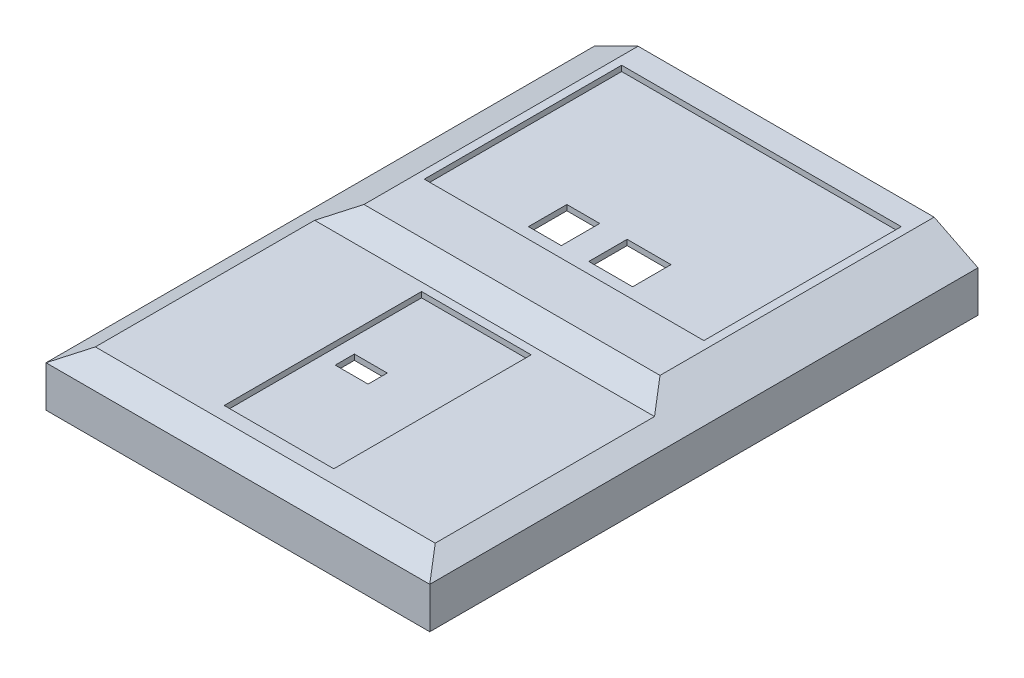
SolidWorks part; units mm, degrees
ref_plane "Ebene vorne" through (0, 0, 0) normal (0, 0, 1) x (1, 0, 0)
ref_plane "Ebene oben" through (0, 0, 0) normal (0, 1, 0) x (1, 0, 0)
ref_plane "Ebene rechts" through (0, 0, 0) normal (1, 0, 0) x (0, 0, -1)
sketch "Skizze1" plane through (0, 0, 0) normal (0, 0, 1) x (1, 0, 0)
  line L1 (-35, -7.5) -> (35, -7.5)
  line L2 (-35, -7.5) -> (-35, 7.5)
  line L3 (-35, 7.5) -> (35, 7.5)
  line L4 (35, -7.5) -> (35, 7.5)
  line L5 (-35, -7.5) -> (35, 7.5) construction
  line L6 (-35, 7.5) -> (35, -7.5) construction
  point P0 (0, 0)
  dimension "D1" = 70
  dimension "D2" = 15
extrude "Aufsatz-Linear austragen1" add sketch "Skizze1" along normal blind 100
sketch "Skizze2" plane through (0, 0, 100) normal (0, 0, 1) x (1, 0, 0)
  line L0 (-35, 7.5) -> (-35, 0)
  line L1 (-35, 7.5) -> (-35, -7.5) construction
  line L2 (-35, 0) -> (-20, 7.5)
  line L3 (35, 7.5) -> (-35, 7.5) construction
  line L4 (-20, 7.5) -> (-35, 7.5)
  dimension "D1" = 15
extrude "Schnitt-Linear austragen1" cut sketch "Skizze2" against normal up to surface (100 mm away) up to face at (0, 0, 0)
ref_plane "Ebene1" through (0, 0, 0) normal (-1, 0, 0) x (0, 0, 1)
mirror "Spiegeln1" about plane through (0, 0, 0) normal (-1, 0, 0) of "Schnitt-Linear austragen1"
sketch "Skizze4" plane through (-35, 0, 0) normal (-1, 0, 0) x (0, 0, 1)
  line L0 (100, 0) -> (95, 2)
  line L1 (95, 2) -> (55, 2)
  line L2 (55, 2) -> (50, 4)
  line L3 (50, 4) -> (0, 4)
  line L5 (0, 7.5) -> (100, 7.5) construction
  line L6 (0, 7.5) -> (100, 7.5)
  line L7 (100, 7.5) -> (100, 0)
  line L8 (0, 0) -> (0, 7.5) construction
  line L9 (0, 4) -> (0, 7.5)
  dimension "D1" = 2
  dimension "D2" = 2
  dimension "D3" = 40
  dimension "D4" = 50
extrude "Schnitt-Linear austragen3" cut sketch "Skizze4" against normal up to surface (70 mm away) up to face at (35, -3.75, 50)
shell "Wandung1" thickness 2 removed face at (0, -7.5, 50)
sketch "Skizze5" plane through (0, 2, 0) normal (0, 1, 0) x (1, 0, 0)
  line L0 (0, 4.125) -> (0, -4.125) construction
  line L1 (-10, -92.5) -> (10, -92.5)
  line L2 (-10, -92.5) -> (-10, -56.5)
  line L3 (-10, -56.5) -> (10, -56.5)
  line L4 (10, -92.5) -> (10, -56.5)
  line L5 (-10, -92.5) -> (10, -56.5) construction
  line L6 (-10, -56.5) -> (10, -92.5) construction
  line L7 (31, -55) -> (-31, -55) construction
  point P0 (0, -74.5)
  dimension "D1" = 36
  dimension "D2" = 20
  dimension "D3" = 1.5
extrude "Schnitt-Linear austragen4" cut sketch "Skizze5" against normal blind 1
sketch "Skizze6" plane through (0, 1, 0) normal (0, 1, 0) x (1, 0, 0)
  line L0 (-10, -56.5) -> (-10, -92.5) construction
  line L1 (-7.25, -71.5) -> (-1.25, -71.5)
  line L2 (-7.25, -71.5) -> (-7.25, -75)
  line L3 (-7.25, -75) -> (-1.25, -75)
  line L4 (-1.25, -71.5) -> (-1.25, -75)
  line L5 (10, -56.5) -> (-10, -56.5) construction
  dimension "D1" = 2.75
  dimension "D2" = 15
  dimension "D3" = 3.5
  dimension "D4" = 6
extrude "Schnitt-Linear austragen5" cut sketch "Skizze6" against normal up to surface (1 mm away) up to face at (0, 0, 74.6148)
sketch "Skizze7" plane through (0, 4, 0) normal (0, 1, 0) x (1, 0, 0)
  line L1 (25.5, -4.5) -> (-25.5, -4.5)
  line L2 (25.5, -4.5) -> (25.5, -40.5)
  line L3 (25.5, -40.5) -> (-25.5, -40.5)
  line L4 (-25.5, -4.5) -> (-25.5, -40.5)
  line L5 (25.5, -4.5) -> (-25.5, -40.5) construction
  line L6 (25.5, -40.5) -> (-25.5, -4.5) construction
  line L7 (27, -50) -> (27, 0) construction
  line L8 (27, 0) -> (-27, 0) construction
  point P0 (0, -22.5)
  dimension "D1" = 51
  dimension "D2" = 36
  dimension "D3" = 1.5
  dimension "D4" = 4.5
extrude "Schnitt-Linear austragen6" cut sketch "Skizze7" against normal blind 1
sketch "Skizze12" plane through (0, 3, 0) normal (0, 1, 0) x (1, 0, 0)
  line L0 (25.5, -40.5) -> (25.5, -4.5) construction
  line L1 (9.5, -37.5) -> (1.5, -37.5)
  line L2 (9.5, -37.5) -> (9.5, -30.5)
  line L3 (9.5, -30.5) -> (1.5, -30.5)
  line L4 (1.5, -37.5) -> (1.5, -30.5)
  line L5 (25.5, -4.5) -> (-25.5, -4.5) construction
  dimension "D1" = 7
  dimension "D2" = 8
  dimension "D3" = 16
  dimension "D4" = 26
extrude "Schnitt-Linear austragen8" cut sketch "Skizze12" against normal up to surface (1 mm away) up to face at (0, 2, 25.8074)
sketch "Skizze13" plane through (0, 0, 0) normal (0, 0, -1) x (-1, 0, 0)
  line L0 (2.5, -7.5) -> (-2.5, -7.5)
  line L1 (35, -7.5) -> (-35, -7.5) construction
  line L2 (-2.5, -7.5) -> (-2.5, -6.2)
  line L3 (-2.5, -6.2) -> (-7.5, -6.2)
  line L4 (-7.5, -6.2) -> (-7.5, -1.9)
  line L5 (-7.5, -1.9) -> (7.5, -1.9)
  line L6 (7.5, -1.9) -> (7.5, -6.2)
  line L7 (7.5, -6.2) -> (2.5, -6.2)
  line L8 (2.5, -6.2) -> (2.5, -7.5)
  line L9 (0, -4.125) -> (0, 4.125) construction
  dimension "D1" = 2.5
  dimension "D2" = 2.5
  dimension "D3" = 5
  dimension "D4" = 5
  dimension "D5" = 1.3
  dimension "D6" = 4.3
extrude "Schnitt-Linear austragen9" cut sketch "Skizze13" against normal blind 1
sketch "Skizze14" plane through (0, 3, 0) normal (0, 1, 0) x (1, 0, 0)
  line L0 (1.5, -30.5) -> (1.5, -37.5) construction
  line L1 (-3.5, -37.5) -> (-9.5, -37.5)
  line L2 (-3.5, -37.5) -> (-3.5, -30.5)
  line L3 (-3.5, -30.5) -> (-9.5, -30.5)
  line L4 (-9.5, -37.5) -> (-9.5, -30.5)
  line L5 (-25.5, -40.5) -> (25.5, -40.5) construction
  dimension "D1" = 5
  dimension "D2" = 6
  dimension "D3" = 3
  dimension "D4" = 7
extrude "Schnitt-Linear austragen10" cut sketch "Skizze14" against normal up to surface (1 mm away) up to face at (5.5, 2, 34)
sketch "Skizze16" plane through (0, -7.5, 0) normal (0, -1, 0) x (1, 0, 0)
  line L9 (31, 2) -> (31, 96)
  line L10 (-31, 96) -> (-31, 2)
  line L11 (31, 96) -> (-31, 96)
  line L12 (31, 2) -> (31, 96)
  line L13 (-31, 96) -> (-31, 2)
  line L14 (31, 96) -> (-31, 96)
  dimension "D1" = 2
extrude "Linear-Austragen-Dünn1" add sketch "Skizze16" along normal blind 2 and the other way up to next thin thin type one direction wall 2
chamfer "Fase1" distance 4 distance2 2 2 edges at (32, -9.5, 2) (-32, -9.5, 2) first distance on face at (0, -9.5, 49.5)
chamfer "Fase2" distance 1 angle 45 3 edges at (33, -9.5, 52) (0, -9.5, 98) (-33, -9.5, 52)
